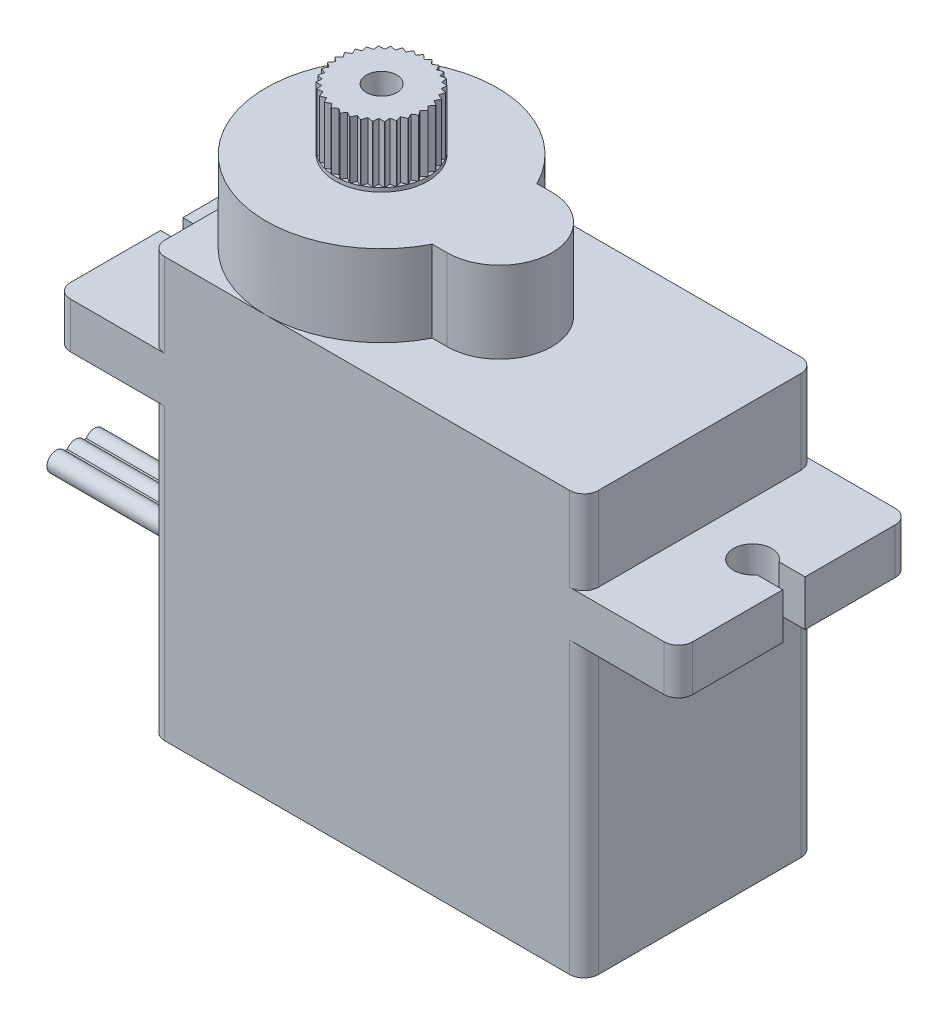
SolidWorks part; units mm, degrees
ref_plane "Plan de face" through (0, 0, 0) normal (0, 0, 1) x (1, 0, 0)
ref_plane "Plan de dessus" through (0, 0, 0) normal (0, 1, 0) x (1, 0, 0)
ref_plane "Plan de droite" through (0, 0, 0) normal (1, 0, 0) x (0, 0, -1)
sketch "Esquisse1" plane through (0, 0, 0) normal (0, 0, 1) x (1, 0, 0)
  line L0 (0, 0) -> (0, 15.2)
  line L1 (0, 15.2) -> (-4.95, 15.2)
  line L2 (-4.95, 15.2) -> (-4.95, 17.6)
  line L3 (-4.95, 17.6) -> (0, 17.6)
  line L4 (0, 17.6) -> (0, 22)
  line L5 (0, 22) -> (22.75, 22)
  line L6 (22.75, 22) -> (22.75, 17.6)
  line L7 (22.75, 17.6) -> (27.7, 17.6)
  line L8 (27.7, 17.6) -> (27.7, 15.2)
  line L9 (27.7, 15.2) -> (22.75, 15.2)
  line L10 (22.75, 15.2) -> (22.75, 0)
  line L11 (22.75, 0) -> (0, 0)
  dimension "D1" = 22.75
  dimension "D2" = 22
  dimension "D3" = 2.4
  dimension "D4" = 4.4
  dimension "D5" = 4.95
extrude "Boss.-Extru.1" add sketch "Esquisse1" along normal blind 12.13
sketch "Esquisse2" plane through (0, 22, 0) normal (0, 1, 0) x (1, 0, 0)
  line L0 (-4.95, -6.065) -> (0, -6.065) construction
  line L1 (-4.95, -12.13) -> (-4.95, 0) construction
  line L2 (0, -12.13) -> (0, 0) construction
  line L3 (-4.95, -6.65) -> (-4.95, -5.48)
  line L4 (-4.95, -5.48) -> (-3.591, -5.48)
  line L6 (-4.95, -6.65) -> (-3.591, -6.65)
  line L7 (11.375, 0) -> (11.375, -12.13) construction
  line L8 (22.75, 0) -> (0, 0) construction
  line L9 (22.75, -12.13) -> (0, -12.13) construction
  line L12 (27.7, -6.065) -> (22.75, -6.065) construction
  line L13 (27.7, -6.65) -> (26.341, -6.65)
  line L14 (27.7, -5.48) -> (26.341, -5.48)
  line L16 (27.7, -5.48) -> (27.7, -6.65)
  circle A0 centre (-2.78, -6.065) radius 1 construction
  arc A1 (-3.591, -6.65) -> (-3.591, -5.48) centre (-2.78, -6.065) ccw
  circle A2 centre (25.53, -6.065) radius 1 construction
  arc A3 (26.341, -6.65) -> (26.341, -5.48) centre (25.53, -6.065) cw
  dimension "D1" = 2.17
  dimension "D3" = 1
  dimension "D2" = 1.17
extrude "Enlèv. mat.-Extru.1" cut sketch "Esquisse2" against normal through all
fillet "Congé1" radius 0.75 12 edges at (27.7, 16.4, 0) (27.7, 16.4, 12.13) (-4.95, 16.4, 0) (-4.95, 16.4, 12.13) (22.75, 7.6, 12.13) (22.75, 19.8, 12.13) (0, 7.6, 12.13) (0, 19.8, 12.13) (0, 19.8, 0) (0, 7.6, 0) (22.75, 7.6, 0) (22.75, 19.8, 0)
sketch "Esquisse3" plane through (0, 22, 0) normal (0, 1, 0) x (1, 0, 0)
  line L0 (0, -11.38) -> (0, -0.75) construction
  line L1 (22, 0) -> (0.75, 0) construction
  line L2 (22, -12.13) -> (0.75, -12.13) construction
  line L3 (0, -6.065) -> (22.75, -6.065) construction
  line L4 (22.75, -11.38) -> (22.75, -0.75) construction
  line L5 (22.75, -11.38) -> (22.75, -0.75) construction
  line L6 (12.25, -3.315) -> (11.4707, -3.315)
  line L7 (12.25, -8.815) -> (11.4707, -8.815)
  circle A0 centre (6.065, -6.065) radius 6.065 construction
  circle A1 centre (12.25, -6.065) radius 2.75 construction
  arc A2 (11.4707, -3.315) -> (11.4707, -8.815) centre (6.065, -6.065) ccw
  arc A3 (12.25, -3.315) -> (12.25, -8.815) centre (12.25, -6.065) cw
  dimension "D1" = 5.5
  dimension "D2" = 10.5
extrude "Boss.-Extru.2" add sketch "Esquisse3" along normal blind 4.27
sketch "Esquisse4" plane through (0, 26.27, 0) normal (0, 1, 0) x (1, 0, 0)
  circle A0 centre (6.065, -6.065) radius 2.43
  dimension "D1" = 4.86
extrude "Boss.-Extru.3" add sketch "Esquisse4" along normal blind 3.21
sketch "Esquisse5" plane through (0, 29.48, 0) normal (0, 1, 0) x (1, 0, 0)
  line L0 (6.065, -6.065) -> (6.065, -3.635) construction
  line L3 (5.85, -3.6445) -> (6.065, -3.6445) construction
  line L4 (6.065, -3.6445) -> (6.28, -3.6445) construction
  line L5 (5.85, -3.6445) -> (6.065, -3.835)
  line L6 (6.065, -3.835) -> (6.28, -3.6445)
  line L7 (6.2984, -3.6462) -> (6.4748, -3.873)
  line L8 (6.4748, -3.873) -> (6.7211, -3.7252)
  line L9 (6.7389, -3.7303) -> (6.8706, -3.9856)
  line L10 (6.8706, -3.9856) -> (7.1399, -3.8856)
  line L11 (7.1564, -3.8939) -> (7.2389, -4.169)
  line L12 (7.2389, -4.169) -> (7.522, -4.1203)
  line L13 (7.5368, -4.1314) -> (7.5673, -4.417)
  line L14 (7.5673, -4.417) -> (7.8545, -4.4211)
  line L15 (7.867, -4.4348) -> (7.8446, -4.7211)
  line L16 (7.8446, -4.7211) -> (8.1261, -4.7779)
  line L17 (8.1359, -4.7936) -> (8.0612, -5.071)
  line L18 (8.0612, -5.071) -> (8.3275, -5.1786)
  line L19 (8.3342, -5.1958) -> (8.2099, -5.4547)
  line L20 (8.2099, -5.4547) -> (8.4519, -5.6094)
  line L21 (8.4553, -5.6276) -> (8.2855, -5.8592)
  line L22 (8.2855, -5.8592) -> (8.495, -6.0558)
  line L23 (8.495, -6.0742) -> (8.2855, -6.2708)
  line L24 (8.2855, -6.2708) -> (8.4553, -6.5024)
  line L25 (8.4519, -6.5206) -> (8.2099, -6.6753)
  line L26 (8.2099, -6.6753) -> (8.3342, -6.9342)
  line L27 (8.3275, -6.9514) -> (8.0612, -7.059)
  line L28 (8.0612, -7.059) -> (8.1359, -7.3364)
  line L29 (8.1261, -7.3521) -> (7.8446, -7.4089)
  line L30 (7.8446, -7.4089) -> (7.867, -7.6952)
  line L31 (7.8545, -7.7089) -> (7.5673, -7.713)
  line L32 (7.5673, -7.713) -> (7.5368, -7.9986)
  line L33 (7.522, -8.0097) -> (7.2389, -7.961)
  line L34 (7.2389, -7.961) -> (7.1564, -8.2361)
  line L35 (7.1399, -8.2444) -> (6.8706, -8.1444)
  line L36 (6.8706, -8.1444) -> (6.7389, -8.3997)
  line L37 (6.7211, -8.4048) -> (6.4748, -8.257)
  line L38 (6.4748, -8.257) -> (6.2984, -8.4838)
  line L39 (6.28, -8.4855) -> (6.065, -8.295)
  line L40 (6.065, -8.295) -> (5.85, -8.4855)
  line L41 (5.8316, -8.4838) -> (5.6552, -8.257)
  line L42 (5.6552, -8.257) -> (5.4089, -8.4048)
  line L43 (5.3911, -8.3997) -> (5.2594, -8.1444)
  line L44 (5.2594, -8.1444) -> (4.9901, -8.2444)
  line L45 (4.9736, -8.2361) -> (4.8911, -7.961)
  line L46 (4.8911, -7.961) -> (4.608, -8.0097)
  line L47 (4.5932, -7.9986) -> (4.5627, -7.713)
  line L48 (4.5627, -7.713) -> (4.2755, -7.7089)
  line L49 (4.263, -7.6952) -> (4.2854, -7.4089)
  line L50 (4.2854, -7.4089) -> (4.0039, -7.3521)
  line L51 (3.9941, -7.3364) -> (4.0688, -7.059)
  line L52 (4.0688, -7.059) -> (3.8025, -6.9514)
  line L53 (3.7958, -6.9342) -> (3.9201, -6.6753)
  line L54 (3.9201, -6.6753) -> (3.6781, -6.5206)
  line L55 (3.6747, -6.5024) -> (3.8445, -6.2708)
  line L56 (3.8445, -6.2708) -> (3.635, -6.0742)
  line L57 (3.635, -6.0558) -> (3.8445, -5.8592)
  line L58 (3.8445, -5.8592) -> (3.6747, -5.6276)
  line L59 (3.6781, -5.6094) -> (3.9201, -5.4547)
  line L60 (3.9201, -5.4547) -> (3.7958, -5.1958)
  line L61 (3.8025, -5.1786) -> (4.0688, -5.071)
  line L62 (4.0688, -5.071) -> (3.9941, -4.7936)
  line L63 (4.0039, -4.7779) -> (4.2854, -4.7211)
  line L64 (4.2854, -4.7211) -> (4.263, -4.4348)
  line L65 (4.2755, -4.4211) -> (4.5627, -4.417)
  line L66 (4.5627, -4.417) -> (4.5932, -4.1314)
  line L67 (4.608, -4.1203) -> (4.8911, -4.169)
  line L68 (4.8911, -4.169) -> (4.9736, -3.8939)
  line L69 (4.9901, -3.8856) -> (5.2594, -3.9856)
  line L70 (5.2594, -3.9856) -> (5.3911, -3.7303)
  line L71 (5.4089, -3.7252) -> (5.6552, -3.873)
  line L72 (5.6552, -3.873) -> (5.8316, -3.6462)
  circle A0 centre (6.065, -6.065) radius 2.43 construction
  arc A1 (5.85, -3.6445) -> (6.28, -3.6445) centre (6.065, -6.065) cw
  circle A2 centre (6.065, -6.065) radius 2.43 construction
  arc A3 (6.2984, -3.6462) -> (6.7211, -3.7252) centre (6.065, -6.065) cw
  arc A4 (6.7389, -3.7303) -> (7.1399, -3.8856) centre (6.065, -6.065) cw
  arc A5 (7.1564, -3.8939) -> (7.522, -4.1203) centre (6.065, -6.065) cw
  arc A6 (7.5368, -4.1314) -> (7.8545, -4.4211) centre (6.065, -6.065) cw
  arc A7 (7.867, -4.4348) -> (8.1261, -4.7779) centre (6.065, -6.065) cw
  arc A8 (8.1359, -4.7936) -> (8.3275, -5.1786) centre (6.065, -6.065) cw
  arc A9 (8.3342, -5.1958) -> (8.4519, -5.6094) centre (6.065, -6.065) cw
  arc A10 (8.4553, -5.6276) -> (8.495, -6.0558) centre (6.065, -6.065) cw
  arc A11 (8.495, -6.0742) -> (8.4553, -6.5024) centre (6.065, -6.065) cw
  arc A12 (8.4519, -6.5206) -> (8.3342, -6.9342) centre (6.065, -6.065) cw
  arc A13 (8.3275, -6.9514) -> (8.1359, -7.3364) centre (6.065, -6.065) cw
  arc A14 (8.1261, -7.3521) -> (7.867, -7.6952) centre (6.065, -6.065) cw
  arc A15 (7.8545, -7.7089) -> (7.5368, -7.9986) centre (6.065, -6.065) cw
  arc A16 (7.522, -8.0097) -> (7.1564, -8.2361) centre (6.065, -6.065) cw
  arc A17 (7.1399, -8.2444) -> (6.7389, -8.3997) centre (6.065, -6.065) cw
  arc A18 (6.7211, -8.4048) -> (6.2984, -8.4838) centre (6.065, -6.065) cw
  arc A19 (6.28, -8.4855) -> (5.85, -8.4855) centre (6.065, -6.065) cw
  arc A20 (5.8316, -8.4838) -> (5.4089, -8.4048) centre (6.065, -6.065) cw
  arc A21 (5.3911, -8.3997) -> (4.9901, -8.2444) centre (6.065, -6.065) cw
  arc A22 (4.9736, -8.2361) -> (4.608, -8.0097) centre (6.065, -6.065) cw
  arc A23 (4.5932, -7.9986) -> (4.2755, -7.7089) centre (6.065, -6.065) cw
  arc A24 (4.263, -7.6952) -> (4.0039, -7.3521) centre (6.065, -6.065) cw
  arc A25 (3.9941, -7.3364) -> (3.8025, -6.9514) centre (6.065, -6.065) cw
  arc A26 (3.7958, -6.9342) -> (3.6781, -6.5206) centre (6.065, -6.065) cw
  arc A27 (3.6747, -6.5024) -> (3.635, -6.0742) centre (6.065, -6.065) cw
  arc A28 (3.635, -6.0558) -> (3.6747, -5.6276) centre (6.065, -6.065) cw
  arc A29 (3.6781, -5.6094) -> (3.7958, -5.1958) centre (6.065, -6.065) cw
  arc A30 (3.8025, -5.1786) -> (3.9941, -4.7936) centre (6.065, -6.065) cw
  arc A31 (4.0039, -4.7779) -> (4.263, -4.4348) centre (6.065, -6.065) cw
  arc A32 (4.2755, -4.4211) -> (4.5932, -4.1314) centre (6.065, -6.065) cw
  arc A33 (4.608, -4.1203) -> (4.9736, -3.8939) centre (6.065, -6.065) cw
  arc A34 (4.9901, -3.8856) -> (5.3911, -3.7303) centre (6.065, -6.065) cw
  arc A35 (5.4089, -3.7252) -> (5.8316, -3.6462) centre (6.065, -6.065) cw
  circle A36 centre (6.065, -6.065) radius 0.8
  point P113 (6.065, -6.065)
  dimension "D1" = 0.43
  dimension "D4" = 1.6
  dimension "D2" = 0.2
  dimension "D3" = 34
extrude "Enlèv. mat.-Extru.2" cut sketch "Esquisse5" against normal blind 3
sketch "Esquisse6" plane through (0, 0, 0) normal (0, 0, -1) x (-1, 0, 0)
  line L0 (-11.375, 17) -> (-11.375, 0) construction
  line L1 (-19.875, 17) -> (-2.875, 17)
  line L2 (-19.875, 17) -> (-19.875, 4)
  line L3 (-19.875, 4) -> (-2.875, 4)
  line L4 (-2.875, 17) -> (-2.875, 4)
  line L5 (-0.75, 0) -> (-22, 0) construction
  dimension "D1" = 17
  dimension "D2" = 13
  dimension "D3" = 4
extrude "Boss.-Extru.4" add sketch "Esquisse6" along normal blind 0.01
sketch "Esquisse7" plane through (0, 0, -0.01) normal (0, 0, -1) x (-1, 0, 0)
  line L0 (-19.875, 17) -> (-19.025, 15.9) construction
  line L1 (-19.025, 15.9) -> (-3.725, 15.9)
  line L2 (-19.025, 15.9) -> (-19.025, 5.1)
  line L3 (-19.025, 5.1) -> (-3.725, 5.1)
  line L4 (-3.725, 15.9) -> (-3.725, 5.1)
  line L5 (-18.725, 15.6) -> (-4.025, 15.6)
  line L6 (-18.725, 15.6) -> (-18.725, 12)
  line L7 (-18.725, 12) -> (-4.025, 12)
  line L8 (-4.025, 15.6) -> (-4.025, 12)
  line L9 (-18.725, 11.7) -> (-4.025, 11.7)
  line L10 (-18.725, 11.7) -> (-18.725, 7.7)
  line L11 (-18.725, 7.7) -> (-4.025, 7.7)
  line L12 (-4.025, 11.7) -> (-4.025, 7.7)
  line L13 (-18.725, 7.4) -> (-4.025, 7.4)
  line L14 (-18.725, 7.4) -> (-18.725, 5.4)
  line L15 (-18.725, 5.4) -> (-4.025, 5.4)
  line L16 (-4.025, 7.4) -> (-4.025, 5.4)
  line L17 (-2.875, 17) -> (-3.725, 15.9) construction
  line L18 (-2.875, 4) -> (-3.725, 5.1) construction
  dimension "D1" = 0.3
  dimension "D2" = 0.3
  dimension "D3" = 0.3
  dimension "D4" = 0.3
  dimension "D5" = 0.3
  dimension "D6" = 0.3
  dimension "D7" = 15.3
  dimension "D8" = 10.8
  dimension "D9" = 2
  dimension "D10" = 3.6
extrude "Boss.-Extru.5" add sketch "Esquisse7" along normal blind 0.01
sketch "Esquisse8" plane through (0, 0, -0.01) normal (0, 0, -1) x (-1, 0, 0)
  line L8 (-4.425, 8.1) -> (-4.425, 11.3)
  line L9 (-18.325, 8.1) -> (-4.425, 8.1)
  line L10 (-18.325, 11.3) -> (-18.325, 8.1)
  line L11 (-4.425, 11.3) -> (-18.325, 11.3)
  line L12 (-4.425, 8.1) -> (-4.425, 11.3)
  line L13 (-18.325, 8.1) -> (-4.425, 8.1)
  line L14 (-18.325, 11.3) -> (-18.325, 8.1)
  line L15 (-4.425, 11.3) -> (-18.325, 11.3)
  dimension "D1" = 0.4
extrude "Boss.-Extru.6" add sketch "Esquisse8" along normal blind 0.01
sketch "Esquisse9" plane through (0, 0, -0.01) normal (0, 0, -1) x (-1, 0, 0)
  text T0 "Tower Pro" font "Dutch801 Rm BT" height 2.19
  text T1 "TM" font "Century Gothic" height 0.88
  text T2 "SG90" font "Century Schoolbook" height 1.58
extrude "Boss.-Extru.7" add sketch "Esquisse9" along normal blind 0.01
sketch "Esquisse10" plane through (0, 0, -0.02) normal (0, 0, -1) x (-1, 0, 0)
  text T0 "Micro Servo" font "Century Gothic" height 1.54
  text T1 "9g" font "Century Gothic" height 1
extrude "Enlèv. mat.-Extru.3" cut sketch "Esquisse10" against normal blind 0.01
sketch "Esquisse11" plane through (0, 0, 0) normal (-1, 0, 0) x (0, 0, 1)
  line L0 (0.75, 4.8) -> (11.38, 4.8) construction
  line L1 (0.75, 15.2) -> (0.75, 0) construction
  line L2 (11.38, 0) -> (11.38, 15.2) construction
  line L3 (11.38, 0) -> (0.75, 0) construction
  line L4 (0.75, 5.05) -> (11.38, 5.05) construction
  line L5 (11.38, 5.05) -> (11.38, 4.55) construction
  line L6 (11.38, 4.55) -> (0.75, 4.55) construction
  line L7 (6.065, 5.05) -> (6.065, 4.8) construction
  line L8 (6.065, 4.8) -> (6.065, 4.55) construction
  line L9 (5.498, 5.05) -> (5.632, 5.05)
  line L10 (6.498, 5.05) -> (6.632, 5.05)
  line L11 (6.632, 4.55) -> (6.498, 4.55)
  line L12 (5.632, 4.55) -> (5.498, 4.55)
  circle A0 centre (6.065, 4.8) radius 0.5 construction
  circle A1 centre (7.065, 4.8) radius 0.5 construction
  circle A2 centre (5.065, 4.8) radius 0.5 construction
  arc A3 (5.498, 5.05) -> (5.498, 4.55) centre (5.065, 4.8) ccw
  arc A4 (5.632, 5.05) -> (6.498, 5.05) centre (6.065, 4.8) cw
  arc A5 (6.632, 5.05) -> (6.632, 4.55) centre (7.065, 4.8) cw
  arc A6 (6.498, 4.55) -> (5.632, 4.55) centre (6.065, 4.8) cw
  dimension "D1" = 1
  dimension "D2" = 4.8
  dimension "D3" = 0.5
extrude "Boss.-Extru.8" add sketch "Esquisse11" along normal blind 10
